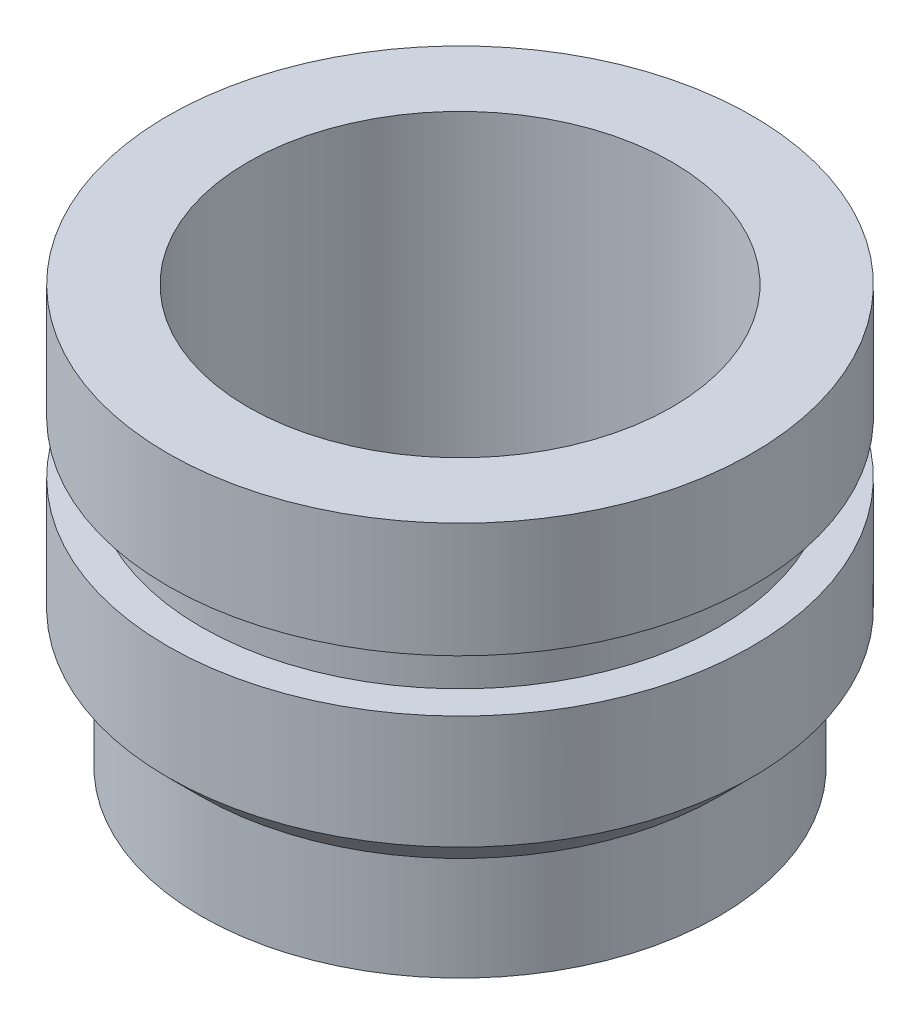
SolidWorks part; units mm, degrees
ref_plane "Front Plane" through (0, 0, 0) normal (0, 0, 1) x (1, 0, 0)
ref_plane "Top Plane" through (0, 0, 0) normal (0, 1, 0) x (1, 0, 0)
ref_plane "Right Plane" through (0, 0, 0) normal (1, 0, 0) x (0, 0, -1)
sketch "Sketch1" plane through (0, 0, 0) normal (0, 1, 0) x (1, 0, 0)
  circle A0 centre (0, 0) radius 1.75
  circle A1 centre (0, 0) radius 1.27
  dimension "D1" = 3.5
  dimension "D2" = 2.54
extrude "Boss-Extrude1" add sketch "Sketch1" against normal blind 2.5
sketch "Sketch2" plane through (0, -2.5, 0) normal (0, -1, 0) x (1, 0, 0)
  circle A0 centre (0, 0) radius 1.55
  circle A3 centre (0, 0) radius 1.75
  circle A4 centre (0, 0) radius 1.75 construction
  dimension "D1" = 3.1
extrude "Cut-Extrude1" cut sketch "Sketch2" against normal blind 0.3125
chamfer "Chamfer1" distance 0.508 angle 45 1 edges at (0, -2.1875, -1.75)
ref_plane "Plane1" through (0, -1, 0) normal (0, 1, 0) x (1, 0, 0)
extrude "Cut-Extrude2" cut sketch "Sketch2<2>" against normal blind 0.3125 from surface starting at plane "Plane1"
sketch "Sketch2<2>" plane through (0, -2.5, 0) normal (0, -1, 0) x (1, 0, 0) same geometry as "Sketch2"
equation "\"D1\"= 3.5mm"
equation "\"D2\"= 3.1mm"
equation "\"ID\"= 2.5mm"
equation "\"D1@Sketch1\"=\"D1\""
equation "\"H\"= 2.5mm"
equation "\"D1@Boss-Extrude1\"=\"H\""
equation "\"D1@Sketch2\"=\"D2\""
equation "\"D1@Cut-Extrude1\"=\"H\"*0.125"
equation "\"D1@Cut-Extrude2\"=\"H\"*0.125"
